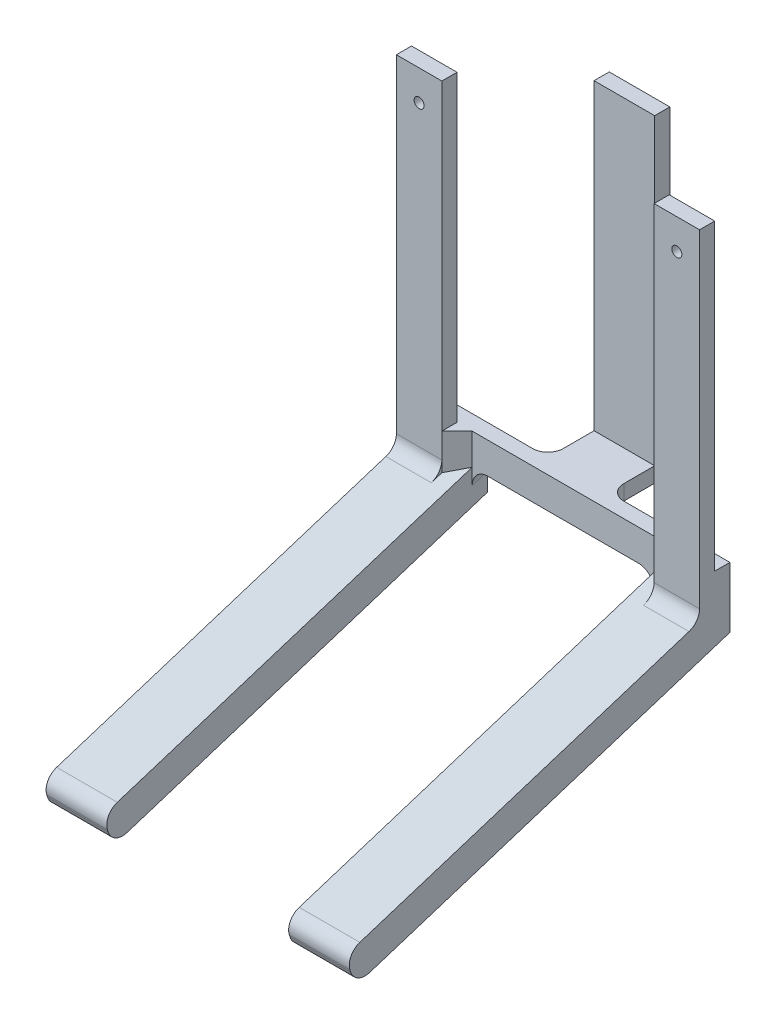
SolidWorks part; units mm, degrees
ref_plane "정면" through (0, 0, 0) normal (0, 0, 1) x (1, 0, 0)
ref_plane "윗면" through (0, 0, 0) normal (0, 1, 0) x (1, 0, 0)
ref_plane "우측면" through (0, 0, 0) normal (1, 0, 0) x (0, 0, -1)
sketch "스케치1" plane through (0, 0, 0) normal (0, 0, 1) x (1, 0, 0)
  line L1 (-10, 100) -> (10, 100)
  line L2 (-10, 100) -> (-10, 0)
  line L3 (-10, 0) -> (10, 0)
  line L4 (10, 100) -> (10, 0)
  dimension "D1" = 100
  dimension "D2" = 20
extrude "보스-돌출1" add sketch "스케치1" along normal blind 5
sketch "스케치2" plane through (0, 0, 0) normal (0, 1, 0) x (1, 0, 0)
  line L0 (-10, -5) -> (-10, 0) construction
  line L1 (-10, 0) -> (10, 0)
  line L2 (-10, 0) -> (-10, -25.2)
  line L3 (-10, -25.2) -> (10, -25.2)
  line L4 (10, 0) -> (10, -25.2)
  line L5 (-10, 0) -> (10, 0) construction
  line L6 (10, -5) -> (10, 0) construction
  line L7 (-10, -5) -> (10, -5) construction
  dimension "D1" = 20.2
extrude "보스-돌출2" add sketch "스케치2" against normal blind 5
sketch "스케치3" plane through (0, 0, 25.2) normal (0, 0, 1) x (1, 0, 0)
  line L1 (-50, 0) -> (50, 0)
  line L2 (-50, 0) -> (-50, -20)
  line L3 (-50, -20) -> (50, -20)
  line L4 (50, 0) -> (50, -20)
  dimension "D1" = 100
  dimension "D2" = 20
extrude "보스-돌출3" add sketch "스케치3" against normal blind 5
sketch "스케치4" plane through (0, 0, 25.2) normal (0, 0, 1) x (1, 0, 0)
  line L0 (0, 0) -> (0, -20) construction
  line L1 (-50, -20) -> (50, -20) construction
  line L2 (50, -20) -> (35, -20)
  line L3 (-50, 100) -> (-35, 100)
  line L4 (-50, 100) -> (-50, -20)
  line L5 (-50, -20) -> (-35, -20)
  line L6 (-35, 100) -> (-35, -20)
  line L7 (50, 100) -> (35, 100)
  line L8 (35, 100) -> (35, -20)
  line L9 (50, 100) -> (50, -20)
  line L10 (10, 100) -> (-10, 100) construction
  dimension "D1" = 15
extrude "보스-돌출4" add sketch "스케치4" along normal blind 5
sketch "스케치5" plane through (0, 0, 0) normal (1, 0, 0) x (0, 0, -1)
  line L0 (-20.2, -20) -> (-143.7636, -59.2603)
  line L1 (-143.7636, -59.2603) -> (-147.016, -49.024)
  line L2 (-147.016, -49.024) -> (-20.2, -8.7303)
  line L3 (-20.2, 0) -> (-20.2, -20) construction
  line L4 (-20.2, -8.7303) -> (-20.2, -20)
  line L5 (-20.2, -20) -> (-19.6613, -20.5669)
extrude "보스-돌출5" add sketch "스케치5" along normal mid plane 100 contours L0 L1 L2 L4
extrude "컷-돌출1" cut sketch "스케치5<3>" against normal mid plane 60 contours L0 L1 L2 L4
sketch "스케치5<3>" plane through (0, 0, 0) normal (1, 0, 0) x (0, 0, -1) same geometry as "스케치5"
fillet "필렛1" radius 5 2 edges at (-42.5, -11.9076, 30.2) (42.5, -11.9076, 30.2)
sketch "스케치6" plane through (0, 0, 30.2) normal (0, 0, 1) x (1, 0, 0)
  line L0 (0, 0) -> (0, 100) construction
  line L1 (10, 100) -> (-10, 100) construction
  line L2 (-35, 100) -> (-50, 100) construction
  line L3 (-50, 100) -> (-50, -8.25) construction
  circle A0 centre (-42.5, 90) radius 1.65
  circle A1 centre (42.5, 90) radius 1.65
  dimension "D1" = 3.3
  dimension "D2" = 10
  dimension "D3" = 7.5
extrude "컷-돌출2" cut sketch "스케치6" against normal blind 60
fillet "필렛2" radius 5 4 edges at (40, -59.2603, 143.7636) (40, -49.024, 147.016) (-40, -59.2603, 143.7636) (-40, -49.024, 147.016)
chamfer "모따기1" distance 5 angle 45 2 edges at (35, -5.1595, 25.2)
fillet "필렛3" radius 5 2 edges at (-30, -9.5246, 22.7) (30, -9.5246, 22.7)
fillet "필렛4" radius 5 3 edges at (10, -2.5, 20.2) (0, -5, 20.2) (-10, -2.5, 20.2)
